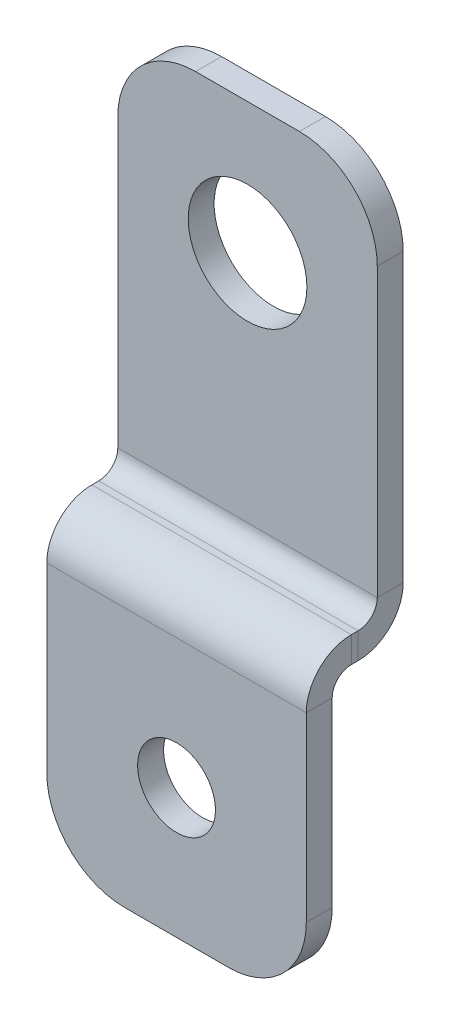
SolidWorks part; units mm, degrees
note: The reader was unsure of these and kept them because the rebuilt part matched: flange length of "Edge-Flange1", "Edge-Flange2".
ref_plane "Ön Düzlem" through (0, 0, 0) normal (0, 0, 1) x (1, 0, 0)
ref_plane "Üst Düzlem" through (0, 0, 0) normal (0, 1, 0) x (1, 0, 0)
ref_plane "Sağ Düzlem" through (0, 0, 0) normal (1, 0, 0) x (0, 0, -1)
sketch "Sketch1" plane through (0, 0, 0) normal (0, 0, 1) x (1, 0, 0)
  line L1 (-514.9742, -14.3503) -> (-504.9742, -14.3503)
  line L2 (-514.9742, -14.3503) -> (-514.9742, -28.4078)
  line L3 (-514.9742, -28.4078) -> (-504.9742, -28.4078)
  line L4 (-504.9742, -14.3503) -> (-504.9742, -28.4078)
  line L6 (-509.9742, -19.4) -> (-504.9742, -19.4) construction
  line L7 (-509.9742, -19.4) -> (-514.9742, -19.4) construction
  circle A0 centre (-509.9742, -19.4) radius 2.2873
  dimension "D1" = 10
base flange "Base-Flange1" sketch "Sketch1" thickness 1 reverse thickness direction yes parameters "D1"=0.7366
edge flange "Edge-Flange1" sketch "Sketch8" flange angle 90 flange length 2 flange position bend outside bend radius 0.7366 thickness 1 relief rectangular parameters "D6"=10
sketch "Sketch8" plane through (0, -28.4078, 1) normal (0, -1, 0) x (1, 0, 0)
  line L0 (-514.9742, 0) -> (-504.9742, 0) construction
  line L1 (-514.9742, 0) -> (-504.9742, 0)
  line L2 (-514.9742, 0) -> (-514.9742, 1)
  line L3 (-514.9742, 1) -> (-504.9742, 1)
  line L4 (-504.9742, 1) -> (-504.9742, 0)
bend "EdgeBend1" bend radius 0.7366 bend angle 90 parameters "D5"=1
edge flange "Edge-Flange2" sketch "Sketch11" flange angle 90 flange length 11.7366 flange position bend outside bend radius 0.7366 thickness 1 relief rectangular parameters "D6"=10
sketch "Sketch11" plane through (0, -30.1444, 2) normal (0, 0, 1) x (-1, 0, 0)
  line L0 (504.9742, 0) -> (514.9742, 0) construction
  line L1 (504.9742, 0) -> (514.9742, 0)
  line L2 (504.9742, 0) -> (504.9742, 10.7366)
  line L3 (504.9742, 10.7366) -> (514.9742, 10.7366)
  line L4 (514.9742, 10.7366) -> (514.9742, 0)
bend "EdgeBend2" bend radius 0.7366 bend angle 90 parameters "D5"=2
sketch "Sketch12" plane through (0, 0, 2.7366) normal (0, 0, -1) x (-1, 0, 0)
  line L0 (509.9742, -30.881) -> (509.9742, -40.881) construction
  line L1 (504.9742, -30.881) -> (514.9742, -30.881) construction
  line L2 (514.9742, -40.881) -> (504.9742, -40.881) construction
  circle A0 centre (509.9742, -35.881) radius 1.5
  dimension "D1" = 3
extrude "Cut-Extrude1" cut sketch "Sketch12" against normal blind 2 normal cut yes
fillet "Fillet1" radius 3 4 edges at (-514.9742, -14.3503, 0.5) (-504.9742, -14.3503, 0.5) (-504.9742, -40.881, 3.2366) (-514.9742, -40.881, 3.2366)
sketch "Büküm-Çizgileri1" [suppressed] plane through (0, 0, 0) normal (0, 1, 0) x (1, 0, 0)
sketch "Sınırlandırma-Kutusu1" [suppressed] plane through (0, 0, 0) normal (0, 1, 0) x (1, 0, 0)
sheet metal parameters "Sheet-Metal2" thickness 1 parameters "D1"=0.7366
flat pattern "Flat-Pattern2" [suppressed]
sketch "Büküm-Çizgileri2" plane through (0, 0, 0) normal (0, 1, 0) x (1, 0, 0)
sketch3d "Sınırlandırma-Kutusu2" [suppressed]
  line L0 (517.4041, -28.4078, 0) -> (502.5443, -28.4078, 0) construction
  line L1 (517.4041, -14.3503, 0) -> (502.5443, -14.3503, 0) construction
  line L2 (517.4041, -28.4078, 0) -> (517.4041, -14.3503, 0) construction
  line L3 (502.5443, -28.4078, 0) -> (502.5443, -14.3503, 0) construction
sheet metal parameters "Sheet-Metal3" thickness 1 parameters "D1"=0.7366
flat pattern "Flat-Pattern2"
sketch "Büküm-Çizgileri2" plane through (0, 0, 0) normal (0, 0, -1) x (-1, 0, 0)
  line L0 (502.5443, -29.379) -> (517.4041, -29.379) construction
  line L1 (502.5443, -29.379) -> (517.4041, -29.379) construction
sketch3d "Sınırlandırma-Kutusu2" [suppressed]
  line L0 (502.5443, -14.3503, 0) -> (502.5443, -33.6137, 0) construction
  line L1 (517.4041, -14.3503, 0) -> (517.4041, -33.6137, 0) construction
  line L2 (502.5443, -14.3503, 0) -> (517.4041, -14.3503, 0) construction
  line L3 (502.5443, -33.6137, 0) -> (517.4041, -33.6137, 0) construction
bend of the flat pattern "Flatten-<EdgeBend1>1"
sheet metal parameters "Sheet-Metal4" thickness 1 parameters "D1"=0.7366
flat pattern "Flat-Pattern2"
sketch "Büküm-Çizgileri2" plane through (0, 0, 0) normal (0, 0, -1) x (-1, 0, 0)
  line L0 (502.5443, -29.379) -> (517.4041, -29.379) construction
  line L1 (502.5443, -29.379) -> (517.4041, -29.379) construction
  line L2 (502.5443, -34.5849) -> (517.4041, -34.5849) construction
  line L3 (502.5443, -34.5849) -> (517.4041, -34.5849) construction
sketch3d "Sınırlandırma-Kutusu2" [suppressed]
  line L0 (502.5443, -14.3503, 0) -> (502.5443, -45.5561, 0) construction
  line L1 (517.4041, -14.3503, 0) -> (517.4041, -45.5561, 0) construction
  line L2 (502.5443, -14.3503, 0) -> (517.4041, -14.3503, 0) construction
  line L3 (502.5443, -45.5561, 0) -> (517.4041, -45.5561, 0) construction
bend of the flat pattern "Flatten-<EdgeBend1>1"
bend of the flat pattern "Flatten-<EdgeBend2>1"
sheet metal parameters "Sheet-Metal5" thickness 1 parameters "D1"=0.7366
flat pattern "Flat-Pattern2"
sketch "Büküm-Çizgileri2" plane through (0, 0, 0) normal (0, 0, -1) x (-1, 0, 0)
  line L0 (504.9742, -29.379) -> (514.9742, -29.379) construction
  line L1 (504.9742, -29.379) -> (514.9742, -29.379) construction
  line L2 (504.9742, -31.5849) -> (514.9742, -31.5849) construction
  line L3 (504.9742, -31.5849) -> (514.9742, -31.5849) construction
sketch3d "Sınırlandırma-Kutusu2" [suppressed]
  line L0 (504.9742, -14.3503, 0) -> (504.9742, -42.5561, 0) construction
  line L1 (514.9742, -14.3503, 0) -> (514.9742, -42.5561, 0) construction
  line L2 (504.9742, -14.3503, 0) -> (514.9742, -14.3503, 0) construction
  line L3 (504.9742, -42.5561, 0) -> (514.9742, -42.5561, 0) construction
bend of the flat pattern "Flatten-<EdgeBend1>1"
bend of the flat pattern "Flatten-<EdgeBend2>1"
